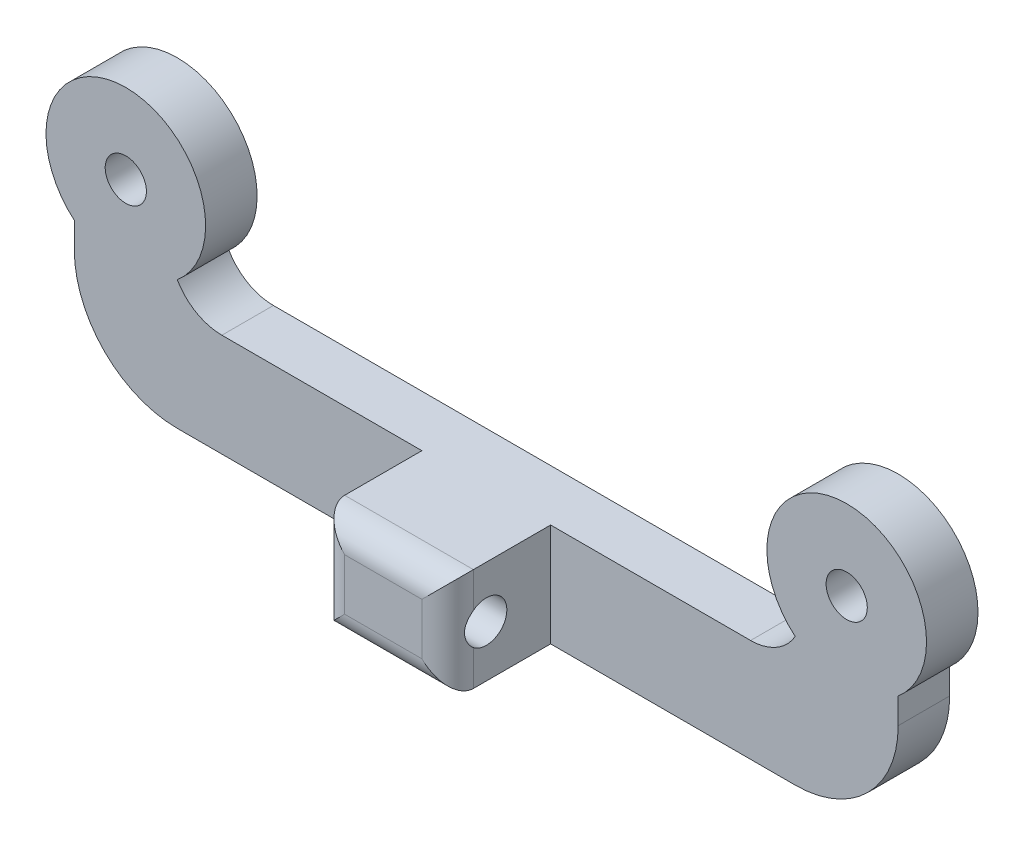
SolidWorks part; units mm, degrees
ref_plane "Alzado" through (0, 0, 0) normal (0, 0, 1) x (1, 0, 0)
ref_plane "Planta" through (0, 0, 0) normal (0, 1, 0) x (1, 0, 0)
ref_plane "Vista lateral" through (0, 0, 0) normal (1, 0, 0) x (0, 0, -1)
sketch "Croquis1" plane through (0, 0, 0) normal (0, 0, 1) x (1, 0, 0)
  line L0 (-4, -4.7371) -> (-4, -14.7371)
  line L1 (-4, -14.7371) -> (60, -14.7371)
  line L2 (4, -4.7371) -> (4, -6.7371)
  line L3 (4, -6.7371) -> (52, -6.7371)
  line L4 (52, -4.7371) -> (52, -6.7371)
  line L5 (60, -4.7371) -> (60, -14.7371)
  line L6 (-4, -4.7371) -> (4, -4.7371) construction
  circle A0 centre (0, 0) radius 1.6
  arc A1 (60, -4.7371) -> (52, -4.7371) centre (56, 0) ccw
  arc A2 (4, -4.7371) -> (-4, -4.7371) centre (0, 0) ccw
  circle A3 centre (56, 0) radius 1.6
  dimension "D1" = 3.2
  dimension "D3" = 8
  dimension "D4" = 12.4
  dimension "D5" = 8
  dimension "D6" = 2
  dimension "D2" = 2
extrude "Saliente-Extruir1" add sketch "Croquis1" along normal blind 4
sketch "Croquis2" plane through (0, 0, 4) normal (0, 0, 1) x (1, 0, 0)
  line L0 (52, -6.7371) -> (4, -6.7371) construction
  line L1 (23, -6.7371) -> (33, -6.7371)
  line L2 (23, -6.7371) -> (23, -14.7371)
  line L3 (23, -14.7371) -> (33, -14.7371)
  line L4 (33, -6.7371) -> (33, -14.7371)
  line L5 (-4, -14.7371) -> (60, -14.7371) construction
  line L7 (4, -6.7371) -> (4, -4.7371) construction
  dimension "D1" = 10
  dimension "D2" = 19
extrude "Saliente-Extruir2" add sketch "Croquis2" along normal blind 8
sketch "Croquis3" plane through (23, 0, 0) normal (-1, 0, 0) x (0, 0, 1)
  line L0 (4, -4.7371) -> (4, -14.7371) construction
  line L1 (12, -6.7371) -> (4, -6.7371) construction
  circle A0 centre (9, -10.7371) radius 1.6
  dimension "D1" = 5
  dimension "D2" = 4
  dimension "D3" = 3.2
extrude "Cortar-Extruir1" cut sketch "Croquis3" against normal up to next
fillet "Redondeo1" radius 2 4 edges at (33, -10.7371, 12) (23, -10.7371, 12) (28, -6.7371, 12) (28, -14.7371, 12)
fillet "Redondeo2" radius 8 2 edges at (60, -14.7371, 2) (-4, -14.7371, 2)
fillet "Redondeo3" radius 4 2 edges at (52, -6.7371, 2) (4, -6.7371, 2)
